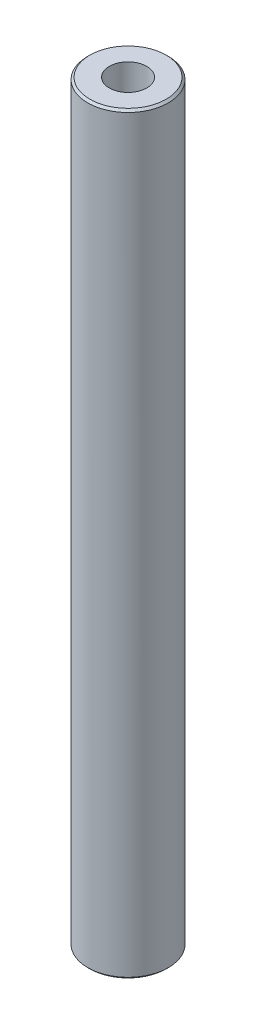
SolidWorks part; units mm, degrees
ref_plane "Front Plane" through (0, 0, 0) normal (0, 0, 1) x (1, 0, 0)
ref_plane "Top Plane" through (0, 0, 0) normal (0, 1, 0) x (1, 0, 0)
ref_plane "Right Plane" through (0, 0, 0) normal (1, 0, 0) x (0, 0, -1)
sketch "Sketch1" plane through (0, 0, 0) normal (0, 1, 0) x (1, 0, 0)
  circle A0 centre (0, 0) radius 7.5
  dimension "SHAFT_OD" = 15
extrude "Boss-Extrude1" add sketch "Sketch1" along normal blind 140.0964
sketch "Sketch2" plane through (0, 0, 0) normal (0, 1, 0) x (1, 0, 0)
  circle A0 centre (0, 0) radius 3.4894
  dimension "BORE_D" = 6.9789
extrude "Cut-Extrude1" cut sketch "Sketch2" along normal through all
chamfer "Chamfer1" distance 0.3942 angle 45 2 edges at (0, 140.0964, 7.5) (0, 0, 7.5)
